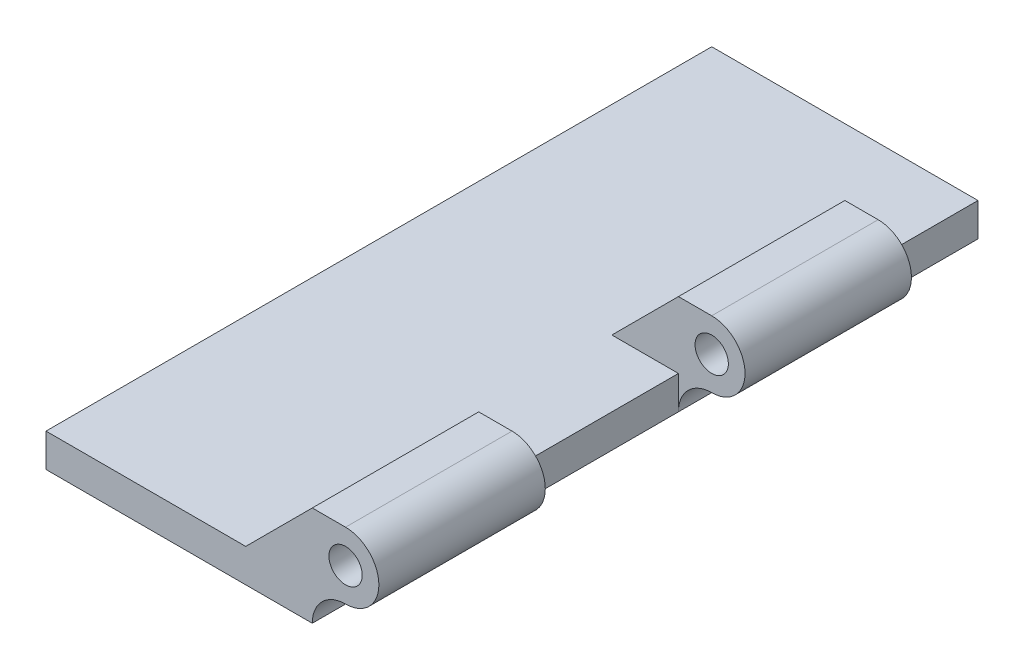
SolidWorks part; units mm, degrees
ref_plane "Front Plane" through (0, 0, 0) normal (0, 0, 1) x (1, 0, 0)
ref_plane "Top Plane" through (0, 0, 0) normal (0, 1, 0) x (1, 0, 0)
ref_plane "Right Plane" through (0, 0, 0) normal (1, 0, 0) x (0, 0, -1)
sketch "Sketch1" plane through (0, 0, 0) normal (0, 1, 0) x (1, 0, 0)
  line L1 (0, 0) -> (8, 0)
  line L2 (0, 0) -> (0, 20)
  line L3 (0, 20) -> (8, 20)
  line L4 (8, 0) -> (8, 20)
  dimension "D1" = 8
  dimension "D2" = 20
extrude "Boss-Extrude1" add sketch "Sketch1" along normal blind 1
sketch "Sketch2" plane through (0, 0, 0) normal (0, 0, 1) x (1, 0, 0)
  line L0 (0, 1) -> (8, 1) construction
  line L1 (8, 1) -> (8, 0) construction
  line L2 (8, 1) -> (9, 1)
  line L3 (9, 3) -> (8, 3)
  line L4 (8, 3) -> (6, 1)
  line L5 (9, 1) -> (9, 2) construction
  line L6 (9, 2) -> (9, 3) construction
  line L7 (8, 1) -> (6, 1)
  line L8 (8, 1) -> (8, 3) construction
  line L9 (8, 0) -> (9, 1) construction
  circle A0 centre (9, 2) radius 0.5
  arc A1 (9, 1) -> (9, 3) centre (9, 2) ccw
  dimension "D1" = 1
  dimension "D2" = 1
  dimension "D3" = 1
  dimension "D4" = 45
extrude "Boss-Extrude2" add sketch "Sketch2" against normal blind 5
fillet "Fillet1" radius 1 1 edges at (8, 1, -2.5)
pattern_linear "LPattern1" count 2 spacing 11 along (0, 0, -1) of "Boss-Extrude2", "Fillet1"
